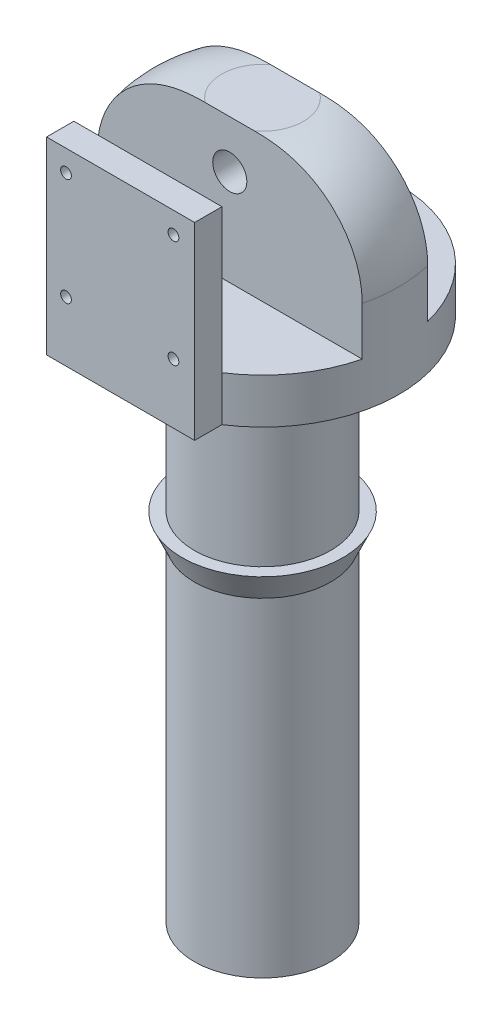
SolidWorks part; units mm, degrees
ref_plane "Front Plane" through (0, 0, 0) normal (0, 0, 1) x (1, 0, 0)
ref_plane "Top Plane" through (0, 0, 0) normal (0, 1, 0) x (1, 0, 0)
ref_plane "Right Plane" through (0, 0, 0) normal (1, 0, 0) x (0, 0, -1)
sketch "Sketch1" plane through (0, 0, 0) normal (0, 1, 0) x (1, 0, 0)
  circle A0 centre (0, 0) radius 12.7
  dimension "D1" = 25.4
extrude "Part that goes into base" add sketch "Sketch1" along normal blind 97.79
sketch "Sketch2" plane through (0, 0, 0) normal (0, 0, 1) x (1, 0, 0)
  line L0 (12.7, 97.79) -> (-12.7, 97.79) construction
  line L1 (12.7, 97.79) -> (-12.7, 97.79)
  line L2 (12.7, 97.79) -> (12.7, 66.294) construction
  line L3 (12.7, 66.294) -> (14.986, 66.294)
  line L4 (14.986, 66.294) -> (12.7, 61.214)
  line L5 (12.7, 61.214) -> (12.7, 66.294)
  line L6 (0, 97.79) -> (0, 52.1662) construction
  dimension "D1" = 31.496
  dimension "D2" = 2.286
  dimension "D3" = 5.08
revolve "Clip in mechanism" add sketch "Sketch2" angle 360 about L6 region at (13.462, 64.6007, 0)
sketch "Sketch3" plane through (0, 97.79, 0) normal (0, 1, 0) x (1, 0, 0)
  circle A0 centre (0, 0) radius 25.4
  dimension "D1" = 50.8
extrude "Top part Extrude" add sketch "Sketch3" along normal blind 35.14
ref_plane "Plane1" through (50.8, 0, 0) normal (1, 0, 0) x (0, 0, -1)
sketch "Sketch4" plane through (50.8, 0, 0) normal (1, 0, 0) x (0, 0, -1)
  line L0 (25.4, 132.93) -> (-25.4, 132.93) construction
  line L1 (25.4, 132.93) -> (-21.336, 132.93)
  line L2 (-12.7, 97.79) -> (12.7, 97.79) construction
  line L8 (6.096, 132.93) -> (6.096, 106.172)
  line L10 (25.4, 97.79) -> (25.4, 132.93) construction
  line L11 (25.4, 106.172) -> (25.4, 132.93)
  line L12 (6.096, 132.93) -> (25.4, 132.93)
  line L13 (25.4, 106.172) -> (6.096, 106.172)
  line L14 (-21.336, 106.172) -> (-6.096, 106.172)
  line L15 (-21.336, 132.93) -> (-6.096, 132.93)
  line L18 (-6.096, 132.93) -> (-6.096, 106.172)
  line L19 (-21.336, 132.93) -> (-21.336, 106.172)
  dimension "D1" = 8.382
  dimension "D3" = 8.382
  dimension "D4" = 19.304
  dimension "D5" = 8.382
  dimension "D6" = 19.304
  dimension "D7" = 4.064
extrude "Cut to Accommodate Encoder" cut sketch "Sketch4" against normal through all
sketch "Sketch5" plane through (0, 106.172, 0) normal (0, 1, 0) x (1, 0, 0)
  line L0 (-13.191, -27.686) -> (15.1785, -27.686)
  line L1 (24.6576, -6.096) -> (24.6576, -40.386)
  line L2 (-24.6576, -6.096) -> (24.6576, -6.096) construction
  line L3 (-24.6576, -6.096) -> (-24.6576, -40.386)
  line L4 (-24.6576, -40.386) -> (24.6576, -40.386)
  arc A0 (24.6576, -6.096) -> (-24.6576, -6.096) centre (0, 0) cw
  dimension "D1" = 21.59
  dimension "D2" = 34.29
sketch "Sketch7" plane through (0, 0, -6.096) normal (0, 0, -1) x (-1, 0, 0)
  line L0 (0, 132.93) -> (0, 124.04) construction
  line L1 (24.6576, 132.93) -> (-24.6576, 132.93) construction
  circle A0 centre (0, 124.04) radius 3.175
  dimension "D2" = 6.35
  dimension "D1" = 8.89
extrude "Bolt Hole" cut sketch "Sketch7" against normal up to surface (12.192 mm away) up to face at (0, 119.551, 6.096)
fillet "Fillet to Accommodate shoulder" radius 17.78 2 edges at (-25.4, 132.93, 0) (25.4, 132.93, 0)
ref_plane "Plane2" through (0, 0, 26.416) normal (0, 0, 1) x (1, 0, 0)
sketch "Sketch9" plane through (0, 0, 26.416) normal (0, 0, 1) x (1, 0, 0)
  line L0 (13.7817, 132.93) -> (-13.7817, 132.93) construction
  line L1 (13.7817, 132.93) -> (-13.7817, 132.93)
  line L2 (-13.7817, 132.93) -> (-13.7817, 97.79)
  line L3 (-25.4, 97.79) -> (25.4, 97.79) construction
  line L4 (-13.7817, 97.79) -> (13.7817, 97.79)
  line L5 (13.7817, 97.79) -> (13.7817, 132.93)
extrude "Boss-Extrude2" add sketch "Sketch9" against normal up to surface (5.08 mm away) up to face at (0, 97.79, 25.4)
sketch "Sketch10" plane through (0, 0, 26.416) normal (0, 0, 1) x (1, 0, 0)
  circle A4 centre (-10.1657, 128.9556) radius 1
  circle A5 centre (9.8343, 128.9556) radius 1
  circle A6 centre (-10.1657, 108.9556) radius 1
  circle A7 centre (9.8343, 108.9556) radius 1
  dimension "D3" = 20
  dimension "D4" = 20
  dimension "D5" = 2
  dimension "D6" = 2
  dimension "D7" = 2
  dimension "D8" = 2
  dimension "D1" = 20
  dimension "D2" = 20
extrude "Cut-Extrude1" cut sketch "Sketch10" against normal up to surface (5.08 mm away) up to face at (0, 119.551, 21.336)
